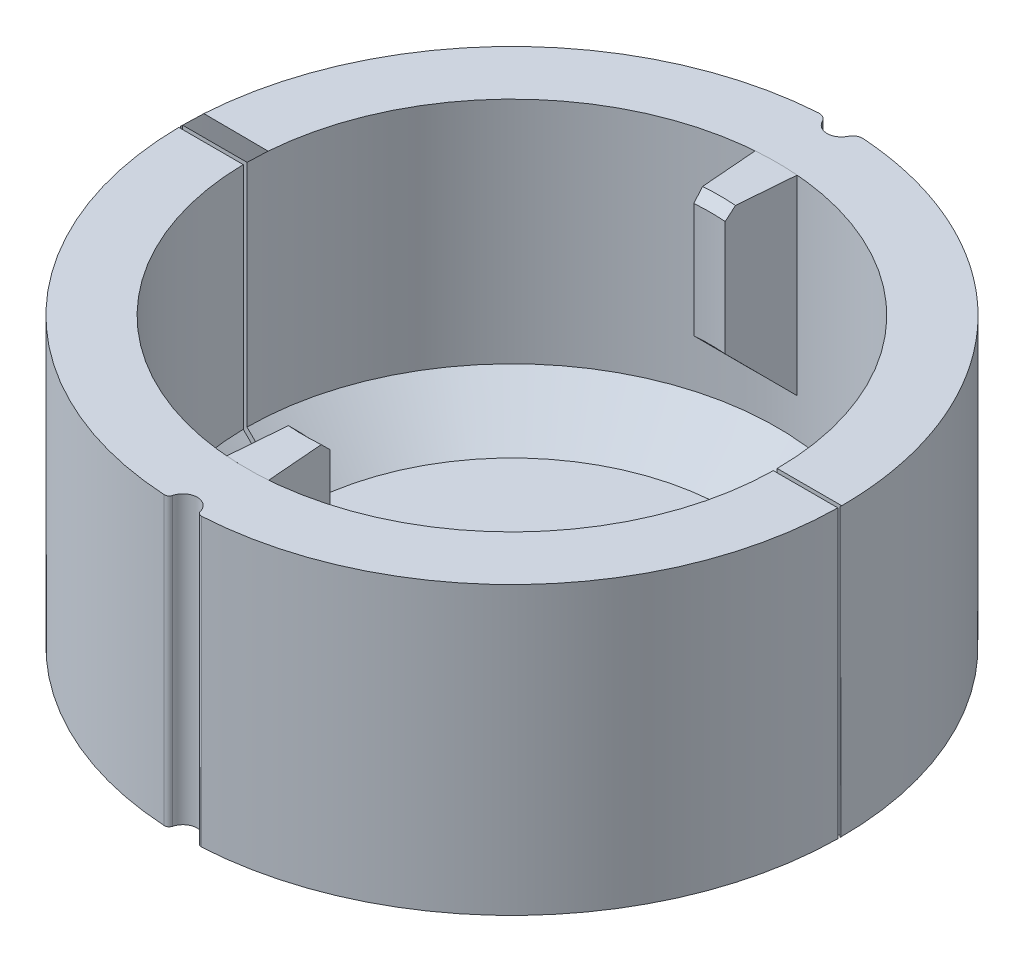
SolidWorks part; units mm, degrees
other "Markup1"
sketch "Sketch4"
other "Markup5"
sketch "Sketch8" plane through (34.5, 25, 34.4428) normal (0.0041, 0.9851, 0.1719) x (0.981, -0.0374, 0.1906)
other "Markup6"
sketch "Sketch9" plane through (34.5, 25, 34.4428) normal (0.0041, 0.9851, 0.1719) x (0.981, -0.0374, 0.1906)
other "Markup7"
sketch "Sketch10" plane through (-34.5, 25, 34.4428) normal (-0.125, 0.9874, 0.0969) x (0.5933, -0.0039, 0.805)
ref_plane "Front Plane" through (0, 0, 0) normal (0, 0, 1) x (1, 0, 0)
ref_plane "Top Plane" through (0, 0, 0) normal (0, 1, 0) x (1, 0, 0)
ref_plane "Right Plane" through (0, 0, 0) normal (1, 0, 0) x (0, 0, -1)
sketch "Sketch1" plane through (0, 0, 0) normal (0, 1, 0) x (1, 0, 0)
  line L3 (0, 0.002) -> (0, 3.7877) construction
  line L4 (0, 3.7877) -> (2.417, 3.7877)
  line L5 (0, 3.7877) -> (-2.417, 3.7877)
  arc A0 (1.9642, -34.442) -> (34.1982, 4.5552) centre (0, 0.002) ccw
  arc A2 (-2.417, 3.7877) -> (2.417, 3.7877) centre (0, 0.002) ccw
  circle A3 centre (0, 0.002) radius 34.5 construction
  arc A7 (-1.3541, 33.8562) -> (1.3541, 33.8562) centre (0, 34.5015) ccw
  arc A8 (34.1982, 4.5552) -> (2.3241, 34.4236) centre (0, 0.002) ccw
  arc A9 (-2.3241, 34.4236) -> (-34.1982, 4.5552) centre (0, 0.002) ccw
  arc A10 (-34.1982, 4.5552) -> (-1.9642, -34.442) centre (0, 0.002) ccw
  arc A11 (1.3541, 33.8562) -> (2.3241, 34.4236) centre (2.2568, 33.4259) cw
  arc A12 (-1.3541, 33.8562) -> (-2.3241, 34.4236) centre (-2.2568, 33.4259) ccw
  arc A13 (1.4518, -34.0686) -> (-1.4518, -34.0686) centre (0, -34.4457) ccw
  arc A14 (1.4518, -34.0686) -> (1.9642, -34.442) centre (1.9358, -33.9428) ccw
  arc A15 (-1.4518, -34.0686) -> (-1.9642, -34.442) centre (-1.9358, -33.9428) cw
  point P15 (1.4997, 34.4694)
  dimension "D2" = 4.834
  dimension "D3" = 4.4915
  dimension "D4" = 34.5
  dimension "D5" = 1
  dimension "D6" = 1.5
  dimension "D7" = 0.5
  dimension "D11" = 1.4997
sketch "Sketch2" plane through (0, 0, 0) normal (0, 1, 0) x (1, 0, 0)
  line L0 (0, 27.75) -> (0, 20.75) construction
  line L1 (-2.1983, 27.6628) -> (0, 27.75) construction
  line L2 (0, 27.75) -> (2.1983, 27.6628) construction
  line L3 (-2.1983, 27.6628) -> (-1.6438, 20.6848)
  line L6 (1.6438, 20.6848) -> (2.1983, 27.6628)
  line L7 (-1.6438, 20.6848) -> (0, 0) construction
  line L8 (0, 0) -> (1.6438, 20.6848) construction
  circle A16 centre (0, 0) radius 27.75
  arc A18 (-1.6438, 20.6848) -> (1.6438, 20.6848) centre (0, 0) cw
  point P3 (0, 20.75)
  dimension "D1" = 55.5
  dimension "D2" = 2.2
  dimension "D3" = 7
extrude "Boss-Extrude1" add sketch "Sketch1" along normal blind 30 contours A10 A0 A8 A7 A9 A2 L5 L4 | L5 A2 L4 region at (0, 0, 0.1522) region at (2.2155, 0, 33.5591)
extrude "Cut-Extrude2" cut sketch "Sketch2" along normal up to next from offset 1 contours A16 | A16 region at (0, 0, 0.2745)
extrude "Boss-Extrude2" add sketch "Sketch2<2>" along normal up to surface (30 mm away) from offset 10 separate body contours A16 region at (0, 0, -24.3928) up to face at (0, 30, 27.75)
sketch "Sketch2<2>" plane through (0, 0, 0) normal (0, 1, 0) x (1, 0, 0) same geometry as "Sketch2"
chamfer "Chamfer2" distance 1 angle 45 1 edges at (0, 30, -20.75)
chamfer "Chamfer3" distance 7 angle 45 1 edges at (0, 10, -20.75)
pattern_circular "CirPattern2" count 2 over 360 about axis through (0, 30, 0) along (0, 1, 0) of bodies 106
fillet "Fillet2" radius 5 1 edges at (0, 1, 27.75) profile chamfer
sketch "Sketch14" plane through (0, 30, 0) normal (0, 1, 0) x (1, 0, 0)
  line L0 (34.4995, -0.1783) -> (-34.4995, -0.1783) construction
  line L1 (-34.4995, 0.0217) -> (-34.4995, -0.3783)
  line L2 (-34.4995, 0.0217) -> (34.4995, 0.0217)
  line L3 (34.4995, 0.0217) -> (34.4995, -0.3783)
  line L4 (34.4995, -0.3783) -> (-34.4995, -0.3783)
  arc A0 (1.9642, -34.442) -> (2.3241, 34.4236) centre (0, 0.002) ccw construction
  arc A1 (-2.3241, 34.4236) -> (-1.9642, -34.442) centre (0, 0.002) ccw construction
  point P12 (-34.4995, -0.1783)
  point P14 (34.4995, -0.1783)
  dimension "D1" = 0.4
extrude "Cut-Extrude4" cut sketch "Sketch14" against normal through all
